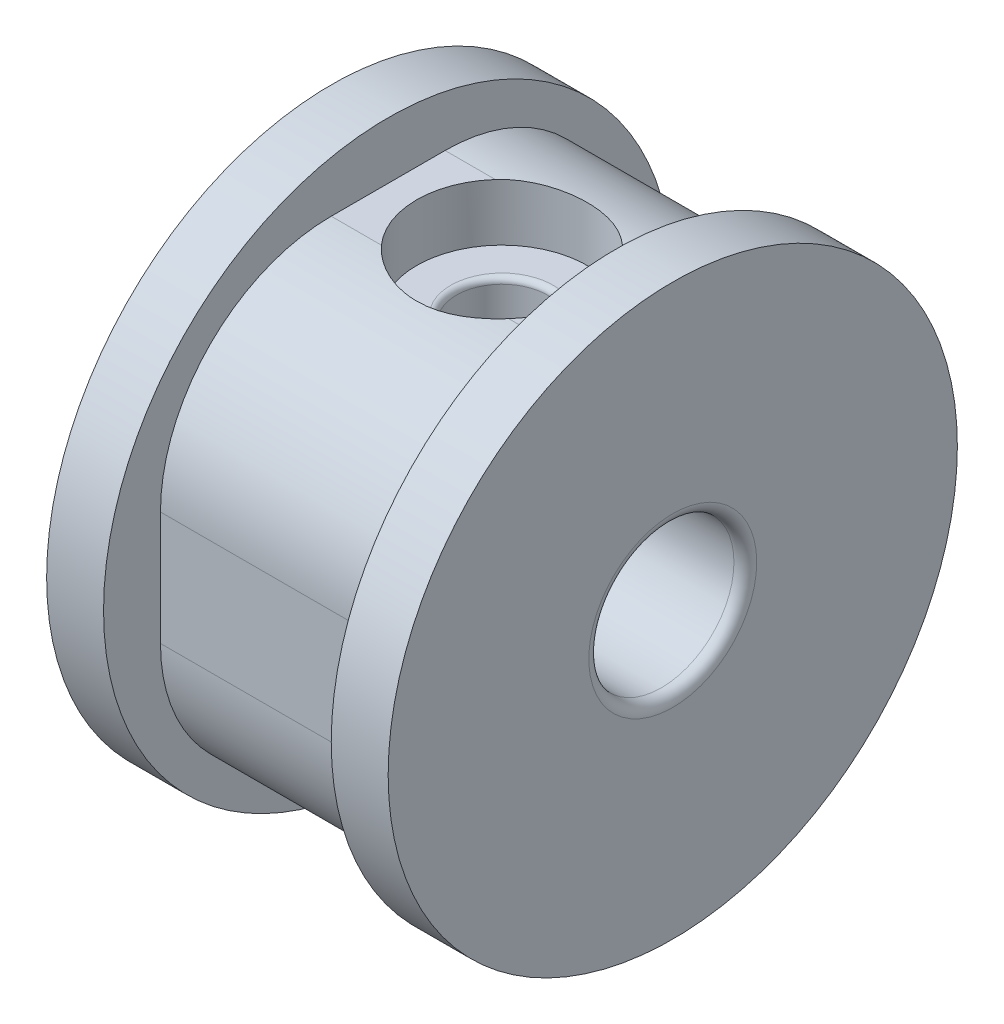
SolidWorks part; units mm, degrees
ref_plane "前视基准面" through (0, 0, 0) normal (0, 0, 1) x (1, 0, 0)
ref_plane "上视基准面" through (0, 0, 0) normal (0, 1, 0) x (1, 0, 0)
ref_plane "右视基准面" through (0, 0, 0) normal (1, 0, 0) x (0, 0, -1)
other "Configuration Table"
sketch "草图1" plane through (0, 0, 0) normal (1, 0, 0) x (0, 0, -1)
  line L1 (0, 0) -> (-16, 0)
  line L2 (0, 0) -> (0, 16)
  line L3 (0, 16) -> (-16, 16)
  line L4 (-16, 0) -> (-16, 16)
  dimension "D1" = 16
  dimension "D2" = 16
extrude "凸台-拉伸1" add sketch "草图1" along normal blind 8
fillet "圆角1" radius 6 4 edges at (4, 0, 0) (4, 0, 16) (4, 16, 0) (4, 16, 16)
sketch "草图3" plane through (0, 16, 0) normal (0, 1, 0) x (1, 0, 0)
  line L0 (4, -6) -> (4, -8) construction
  line L1 (8, -6) -> (0, -6) construction
  circle A0 centre (4, -8) radius 1.6
  dimension "D2" = 3.2
  dimension "D1" = 2
extrude "切除-拉伸1" cut sketch "草图3" against normal blind 4
sketch "草图4" plane through (0, 16, 0) normal (0, 1, 0) x (1, 0, 0)
  circle A0 centre (4, -8) radius 3
  dimension "D1" = 6
extrude "切除-拉伸2" cut sketch "草图4" against normal blind 2
sketch "草图7" plane through (8, 0, 0) normal (1, 0, 0) x (0, 0, -1)
  line L0 (-8, 16) -> (-8, 8) construction
  line L1 (-6, 16) -> (-10, 16) construction
  circle A1 centre (-8, 8) radius 10
  dimension "D1" = 20
  dimension "D2" = 8
extrude "凸台-拉伸2" add sketch "草图7" along normal blind 2
sketch "草图8" plane through (0, 0, 0) normal (-1, 0, 0) x (0, 0, 1)
  circle A1 centre (8, 8) radius 10 construction
  circle A2 centre (8, 8) radius 10
extrude "凸台-拉伸3" add sketch "草图8" along normal blind 2
sketch "草图9" plane through (-2, 0, 0) normal (-1, 0, 0) x (0, 0, 1)
  circle A1 centre (8, 8) radius 2.55
  circle A5 centre (8, 8) radius 10 construction
  dimension "D1" = 5.1
  dimension "D2" = 0
extrude "切除-拉伸4" cut sketch "草图9" against normal blind 22
fillet "圆角2" radius 0.2 1 edges at (4, 14, 9.6)
fillet "圆角3" radius 0.4 2 edges at (-2, 8, 10.55) (10, 8, 5.45)
